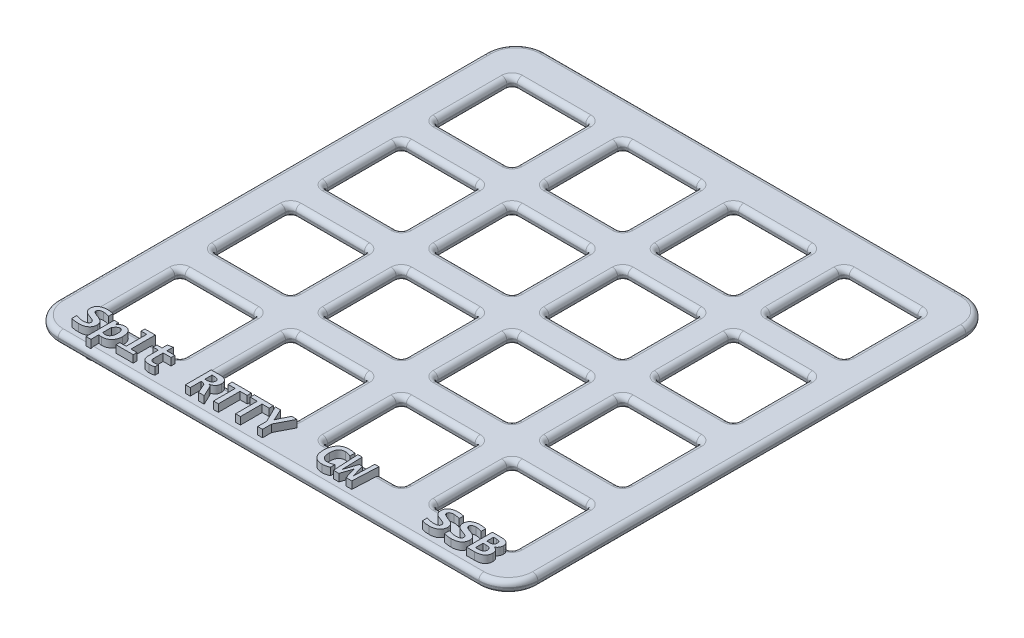
SolidWorks part; units mm, degrees
ref_plane "Front" through (0, 0, 0) normal (0, 0, 1) x (1, 0, 0)
ref_plane "Top" through (0, 0, 0) normal (0, 1, 0) x (1, 0, 0)
ref_plane "Right" through (0, 0, 0) normal (1, 0, 0) x (0, 0, -1)
sketch "Sketch1" plane through (0, 0, 0) normal (0, 1, 0) x (1, 0, 0)
  line L1 (-14.8807, -14.5355) -> (42.1193, -14.5355)
  line L2 (-18.8807, -18.5355) -> (-18.8807, -76.5355)
  line L3 (-14.8807, -80.5355) -> (42.1193, -80.5355)
  line L4 (46.1193, -18.5355) -> (46.1193, -76.5355)
  arc A0 (-14.8807, -14.5355) -> (-18.8807, -18.5355) centre (-14.8807, -18.5355) ccw
  arc A1 (46.1193, -18.5355) -> (42.1193, -14.5355) centre (42.1193, -18.5355) ccw
  arc A2 (42.1193, -80.5355) -> (46.1193, -76.5355) centre (42.1193, -76.5355) ccw
  arc A3 (-18.8807, -76.5355) -> (-14.8807, -80.5355) centre (-14.8807, -76.5355) ccw
  dimension "D1" = 65
  dimension "D2" = 66
extrude "main" add sketch "Sketch1" along normal blind 1.5
sketch "Sketch2" plane through (0, 1.5, 0) normal (0, 1, 0) x (1, 0, 0)
  line L0 (42.1193, -14.5355) -> (-14.8807, -14.5355) construction
  line L1 (-14.2307, -19.6855) -> (-3.5307, -19.6855)
  line L2 (-14.2307, -19.6855) -> (-14.2307, -30.3855)
  line L3 (-14.2307, -30.3855) -> (-3.5307, -30.3855)
  line L4 (-3.5307, -19.6855) -> (-3.5307, -30.3855)
  line L5 (-18.8807, -18.5355) -> (-18.8807, -76.5355) construction
  point P4 (-8.8807, -19.6855)
  dimension "D1" = 5.15
  dimension "D2" = 4.65
  dimension "D3" = 10.7
  dimension "D4" = 10.7
extrude "button hole 1" cut sketch "Sketch2" against normal through all
fillet "button fillet" radius 0.7 12 edges at (-8.8807, 0, 30.3855) (-8.8807, 1.5, 30.3855) (-8.8807, 0, 19.6855) (-8.8807, 1.5, 19.6855) (-3.5307, 0.75, 30.3855) (-3.5307, 0, 25.0355) (-3.5307, 0.75, 19.6855) (-3.5307, 1.5, 25.0355) (-14.2307, 0.75, 19.6855) (-14.2307, 0, 25.0355) (-14.2307, 0.75, 30.3855) (-14.2307, 1.5, 25.0355)
pattern_linear "buttons by 16" count 4 spacing 15 along (1, 0, 0) count 4 spacing 15 along (0, 0, 1) of "button fillet", "button hole 1"
fillet "outer edge fillet" radius 0.7 16 edges at (13.6193, 1.5, 14.5355) (13.6193, 0, 14.5355) (46.1193, 1.5, 47.5355) (46.1193, 0, 47.5355) (13.6193, 1.5, 80.5355) (13.6193, 0, 80.5355) (-18.8807, 1.5, 47.5355) (-18.8807, 0, 47.5355) (44.9477, 1.5, 15.7071) (44.9477, 1.5, 79.364) (-17.7092, 1.5, 79.364) (-17.7092, 1.5, 15.7071) (44.9477, 0, 15.7071) (44.9477, 0, 79.364) (-17.7092, 0, 79.364) (-17.7092, 0, 15.7071)
sketch "Lettering" plane through (0, 0, 0) normal (0, 1, 0) x (1, 0, 0)
  line L0 (45.4193, -34.1355) -> (-18.1807, -34.1355) construction
  line L1 (45.4783, -49.1355) -> (-16.5217, -49.1355) construction
  line L2 (45.4193, -76.5355) -> (45.4193, -18.5355) construction
  line L3 (-18.1807, -18.5355) -> (-18.1807, -76.5355) construction
  line L5 (45.4193, -64.1355) -> (-18.1807, -64.1355) construction
  line L6 (45.4193, -76.5355) -> (45.4193, -18.5355) construction
  line L7 (-18.1807, -18.5355) -> (-18.1807, -76.5355) construction
  line L8 (45.4193, -79.1355) -> (-18.1807, -79.1355) construction
  line L11 (-14.8807, -80.5355) -> (42.1193, -80.5355) construction
  text T0 "SSB" font "Consolas" height 3.5
  text T1 "CW" font "Consolas" height 3.5
  text T2 "RTTY" font "Consolas" height 3.5
  text T3 "Splt" font "Consolas" height 3.5
  dimension "D1" = 1.4
  dimension "D2" = 16.4
  dimension "D3" = 31.4
  dimension "D4" = 46.4
extrude "lettering boss" add sketch "Lettering" along normal blind 2.5
